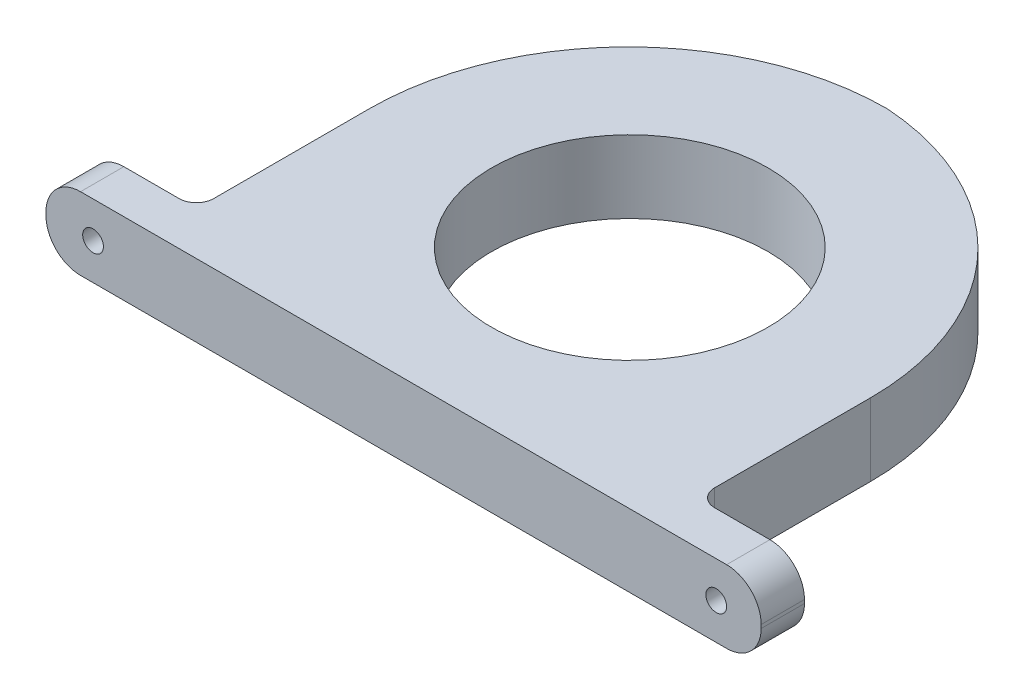
SolidWorks part; units mm, degrees
ref_plane "Front Plane" through (0, 0, 0) normal (0, 0, 1) x (1, 0, 0)
ref_plane "Top Plane" through (0, 0, 0) normal (0, 1, 0) x (1, 0, 0)
ref_plane "Right Plane" through (0, 0, 0) normal (1, 0, 0) x (0, 0, -1)
sketch "Sketch1" plane through (0, 0, 0) normal (0, 1, 0) x (1, 0, 0)
  line L0 (0.1912, 17.2527) -> (0.1912, -52.7952) construction
  line L1 (0.1912, -52.5349) -> (103.1912, -52.5349)
  line L2 (103.1912, -52.5349) -> (103.1912, -40)
  line L3 (103.1912, -40) -> (72.1912, -40)
  line L4 (72.1912, -40) -> (72.1912, 85)
  line L5 (72.1912, 85) -> (0.1912, 85)
  line L6 (0.1912, -52.5349) -> (-103.8088, -52.5349)
  line L7 (-103.8088, -52.5349) -> (-103.8088, -40)
  line L8 (-103.8088, -40) -> (-72.8088, -40)
  line L9 (-72.8088, -40) -> (-72.8088, 85)
  line L10 (-72.8088, 85) -> (0.1912, 85)
  line L11 (-72.8088, 12.9464) -> (72.1912, 12.9464) construction
  circle A2 centre (-0.3088, 12.9464) radius 40
  dimension "D1" = 31
  dimension "D2" = 125
  dimension "D3" = 31
  dimension "D4" = 12.5349
  dimension "D5" = 145
extrude "Boss-Extrude1" add sketch "Sketch1" along normal blind 21
fillet "Fillet1" radius 10 1 edges at (103.1912, 21, 46.2675)
fillet "Fillet2" radius 10 1 edges at (-103.8088, 21, 46.2675)
fillet "Fillet3" radius 10 1 edges at (-103.8088, 0, 46.2675)
fillet "Fillet4" radius 10 1 edges at (103.1912, 0, 46.2675)
fillet "Fillet5" radius 5 1 edges at (72.1912, 10.5, 40)
fillet "Fillet6" radius 5 1 edges at (-72.8088, 10.5, 40)
fillet "Fillet7" radius 75 1 edges at (-72.8088, 10.5, -85)
fillet "Fillet8" radius 75 1 edges at (72.1912, 10.5, -85)
sketch "Sketch2" plane through (0, 0, 40) normal (0, 0, -1) x (-1, 0, 0)
  line L0 (-103.1912, 10.5) -> (-77.1912, 10.5) construction
  line L1 (-103.1912, 11) -> (-103.1912, 10) construction
  line L2 (-77.1912, 0) -> (-77.1912, 21) construction
  line L3 (-90.1912, 10.5) -> (-90.1912, 21) construction
  line L4 (-93.1912, 21) -> (-77.1912, 21) construction
  line L7 (0, 8.3106) -> (0, 120.578) construction
  circle A0 centre (-90.1912, 10.5) radius 3
  circle A2 centre (90.1912, 10.5) radius 3
extrude "Cut-Extrude1" cut sketch "Sketch2" against normal through all
